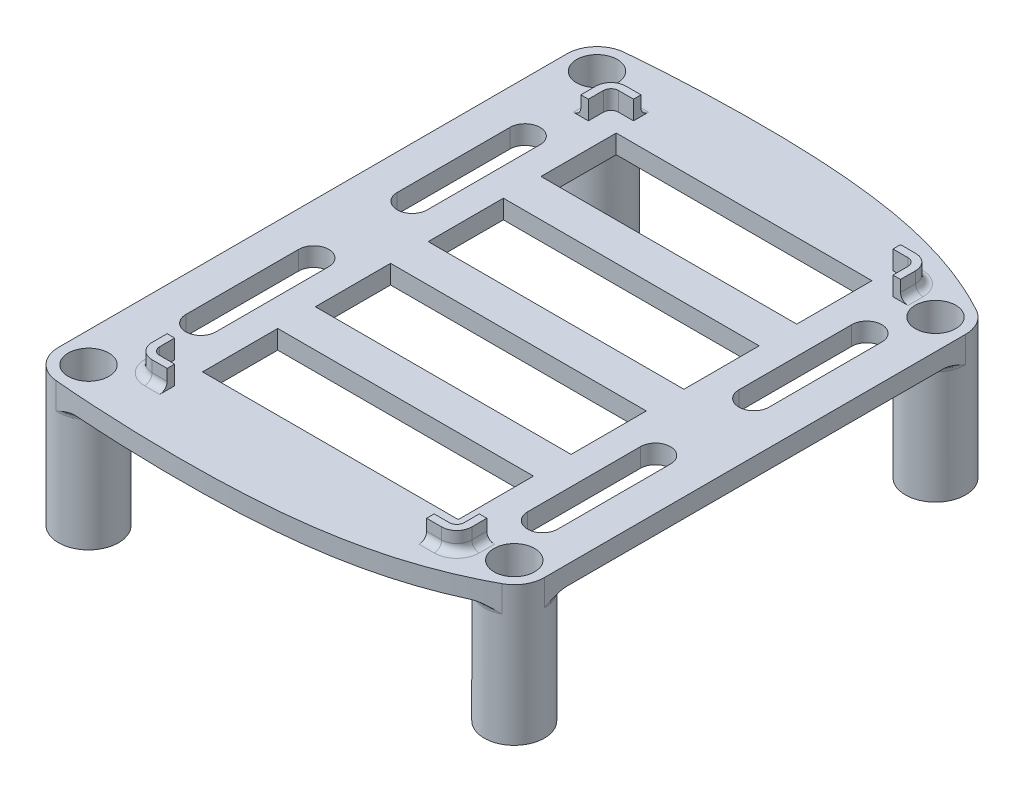
SolidWorks part; units mm, degrees
ref_plane "前视基准面" through (0, 0, 0) normal (0, 0, 1) x (1, 0, 0)
ref_plane "上视基准面" through (0, 0, 0) normal (0, 1, 0) x (1, 0, 0)
ref_plane "右视基准面" through (0, 0, 0) normal (1, 0, 0) x (0, 0, -1)
other "Configuration Table"
sketch "草图1" plane through (0, 0, 0) normal (0, 1, 0) x (1, 0, 0)
  line L0 (0, 35.4779) -> (0, -35.3561) construction
  line L1 (-47.5, 31) -> (-41.5, 31)
  line L2 (-47.5, 25) -> (-47.5, -25)
  line L3 (-47.5, -31) -> (-41.5, -31)
  line L4 (47.5, 25) -> (47.5, -25)
  line L5 (-47.5, 31) -> (47.5, -31) construction
  line L6 (-47.5, -31) -> (47.5, 31) construction
  line L9 (-41.5, 31) -> (-41.5, 41)
  line L11 (-29.5, 31) -> (-29.5, 41)
  line L12 (29.5, 31) -> (29.5, 41)
  line L14 (41.5, 31) -> (41.5, 41)
  line L15 (-78.7463, 0) -> (58.6748, 0) construction
  line L16 (41.5, -31) -> (41.5, -41)
  line L18 (29.5, -31) -> (29.5, -41)
  line L21 (-29.5, -31) -> (-29.5, -41)
  line L23 (-41.5, -31) -> (-41.5, -41)
  line L24 (-29.5, 31) -> (-3, 31)
  line L25 (41.5, 31) -> (47.5, 31)
  line L26 (41.5, -31) -> (47.5, -31)
  line L27 (-29.5, -31) -> (-3, -31)
  line L28 (47.5, 31) -> (50.8, 31)
  line L29 (-47.5, 31) -> (-50.8, 31)
  line L31 (-47.5, 25) -> (-50.8, 25)
  line L33 (47.5, 25) -> (50.8, 25)
  line L36 (47.5, -25) -> (50.8, -25)
  line L37 (47.5, -31) -> (50.8, -31)
  line L38 (-47.5, -31) -> (-50.8, -31)
  line L39 (-47.5, -25) -> (-50.8, -25)
  line L41 (-3, -33.8) -> (-3, -31)
  line L43 (-3, 33.8) -> (-3, 31)
  line L45 (3, 33.8) -> (3, 31)
  line L47 (3, -33.8) -> (3, -31)
  line L48 (3, 31) -> (29.5, 31)
  line L49 (3, -31) -> (29.5, -31)
  arc A0 (-41.5, 41) -> (-29.5, 41) centre (-35.5, 41) cw
  arc A1 (-41.5, -41) -> (-29.5, -41) centre (-35.5, -41) ccw
  arc A2 (41.5, -41) -> (29.5, -41) centre (35.5, -41) cw
  arc A3 (41.5, 41) -> (29.5, 41) centre (35.5, 41) ccw
  arc A4 (-50.8, 31) -> (-50.8, 25) centre (-50.8, 28) ccw
  circle A5 centre (-50.8, 28) radius 1.5
  circle A6 centre (50.8, 28) radius 1.5
  arc A7 (50.8, 31) -> (50.8, 25) centre (50.8, 28) cw
  circle A8 centre (50.8, -28) radius 1.5
  arc A9 (50.8, -31) -> (50.8, -25) centre (50.8, -28) ccw
  circle A10 centre (-50.8, -28) radius 1.5
  arc A11 (-50.8, -31) -> (-50.8, -25) centre (-50.8, -28) cw
  arc A12 (-3, 33.8) -> (3, 33.8) centre (0, 33.8) cw
  circle A13 centre (0, 33.8) radius 1.5
  circle A14 centre (0, -33.8) radius 1.5
  arc A15 (-3, -33.8) -> (3, -33.8) centre (0, -33.8) ccw
  point P0 (0, 0)
  dimension "D8" = 2.8
  dimension "D1" = 95
  dimension "D2" = 62
  dimension "D3" = 83
  dimension "D4" = 12
  dimension "D5" = 10
  dimension "D6" = 3.3
  dimension "D7" = 6
  dimension "D9" = 6
extrude "凸台-拉伸1" add sketch "草图1" against normal blind 15
sketch "草图2" plane through (0, -15, 0) normal (0, -1, 0) x (1, 0, 0)
  line L0 (-63.1336, 0) -> (63.5579, 0) construction
  line L1 (-57.0239, 31) -> (-3, 31)
  line L2 (-57.0239, 31) -> (-57.0239, 48.5806)
  line L3 (-57.0239, 48.5806) -> (57.0239, 48.5806)
  line L4 (57.0239, 31) -> (57.0239, 48.5806)
  line L5 (0, 56.9992) -> (0, -44.1169) construction
  line L6 (3, 33.8) -> (3, 31) construction
  line L7 (-3, 31) -> (-3, 33.8) construction
  line L8 (3, 33.8) -> (3, 31)
  line L9 (-3, 31) -> (-3, 33.8)
  line L10 (3, 31) -> (57.0239, 31)
  line L11 (3, -33.8) -> (3, -31)
  line L12 (-3, -31) -> (-3, -33.8)
  line L13 (-57.0239, -31) -> (-3, -31)
  line L14 (-57.0239, -31) -> (-57.0239, -48.5806)
  line L15 (-57.0239, -48.5806) -> (57.0239, -48.5806)
  line L16 (57.0239, -31) -> (57.0239, -48.5806)
  line L17 (3, -31) -> (57.0239, -31)
  arc A0 (3, 33.8) -> (-3, 33.8) centre (0, 33.8) ccw construction
  arc A1 (3, 33.8) -> (-3, 33.8) centre (0, 33.8) ccw
  arc A2 (3, -33.8) -> (-3, -33.8) centre (0, -33.8) cw
extrude "切除-拉伸1" cut sketch "草图2" against normal blind 11
sketch "草图3" plane through (0, -15, 0) normal (0, -1, 0) x (1, 0, 0)
  line L0 (47.5, 25) -> (47.5, -25) construction
  line L1 (-45, -28.5) -> (45, -28.5)
  line L2 (-45, -28.5) -> (-45, 28.5)
  line L3 (-45, 28.5) -> (45, 28.5)
  line L4 (45, -28.5) -> (45, 28.5)
  line L5 (-45, -28.5) -> (45, 28.5) construction
  line L6 (-45, 28.5) -> (45, -28.5) construction
  line L7 (-50.8, 31) -> (-3, 31) construction
  point P0 (0, 0)
  dimension "D1" = 2.5
  dimension "D2" = 2.5
extrude "切除-拉伸2" cut sketch "草图3" against normal blind 12
sketch "草图4" plane through (0, -4, 0) normal (0, -1, 0) x (1, 0, 0)
  line L0 (-29.5, 41) -> (-41.5, 41) construction
  line L1 (-71.7869, 0) -> (71.1524, 0) construction
  line L2 (0, 61.1393) -> (0, -47.8922) construction
  circle A0 centre (-35.5, 41) radius 2.8
  circle A1 centre (35.5, 41) radius 2.8
  circle A2 centre (35.5, -41) radius 2.8
  circle A3 centre (-35.5, -41) radius 2.8
extrude "凸台-拉伸2" add sketch "草图4" along normal blind 3.3 separate body
sketch "草图5" plane through (0, -7.3, 0) normal (0, -1, 0) x (1, 0, 0)
  line L0 (-58.868, 0) -> (56.1189, 0) construction
  line L1 (0, 46.5823) -> (0, -51.4835) construction
  circle A0 centre (-35.5, 41) radius 1.5
  circle A1 centre (35.5, 41) radius 1.5
  circle A2 centre (35.5, -41) radius 1.5
  circle A3 centre (-35.5, -41) radius 1.5
extrude "凸台-拉伸3" add sketch "草图5" along normal blind 1.3 separate body
sketch "草图6" plane through (0, -15, 0) normal (0, -1, 0) x (1, 0, 0)
  line L0 (-50.8, 31) -> (-3, 31) construction
  line L1 (-47.5, 31) -> (47.5, 31)
  line L2 (-47.5, 31) -> (-47.5, -31)
  line L3 (-47.5, -31) -> (47.5, -31)
  line L4 (47.5, 31) -> (47.5, -31)
  line L5 (50.8, -31) -> (3, -31) construction
extrude "切除-拉伸3" cut sketch "草图6" against normal blind 5
sketch "草图7" plane through (0, -3, 0) normal (0, -1, 0) x (1, 0, 0)
  line L0 (-60.2485, 0) -> (64.067, 0) construction
  line L1 (0, 41.3678) -> (0, -47.8169) construction
  line L2 (-30, -19) -> (30, -19)
  line L3 (-30, 21) -> (-2, 21)
  line L4 (-30, 21) -> (-30, 19)
  line L5 (-30, 19) -> (30, 19)
  line L6 (30, 21) -> (30, 19)
  line L7 (-30, 21) -> (30, 19) construction
  line L8 (-30, 19) -> (30, 21) construction
  line L9 (30, -21) -> (30, -19)
  line L10 (-30, -21) -> (-2, -21)
  line L11 (-30, -21) -> (-30, -19)
  line L12 (45, 28.5) -> (-45, 28.5) construction
  line L13 (-2, 28.5) -> (2, 28.5)
  line L14 (-2, 28.5) -> (-2, 21)
  line L16 (2, 28.5) -> (2, 21)
  line L18 (2, -28.5) -> (2, -21)
  line L19 (-2, -28.5) -> (2, -28.5)
  line L20 (-2, -28.5) -> (-2, -21)
  line L21 (2, 21) -> (30, 21)
  line L22 (2, -21) -> (30, -21)
  point P5 (0, 20)
  dimension "D1" = 19
  dimension "D2" = 2
  dimension "D3" = 60
  dimension "D4" = 4
extrude "凸台-拉伸4" add sketch "草图7" along normal blind 2.5 separate body
sketch "草图9" plane through (0, -10, 0) normal (0, -1, 0) x (1, 0, 0)
  line L0 (-45, 28.5) -> (45, 28.5) construction
  line L1 (41.5, 31) -> (32, 31)
  line L2 (41.5, 31) -> (41.5, 28.5)
  line L3 (41.5, 28.5) -> (32, 28.5)
  line L4 (32, 31) -> (32, 28.5)
  dimension "D1" = 9.5
extrude "切除-拉伸4" cut sketch "草图9" against normal blind 5
sketch "草图10" plane through (0, 0, 0) normal (0, 1, 0) x (1, 0, 0)
  line L1 (-34.25, -14) -> (34.25, -14)
  line L2 (-36.25, -12) -> (-36.25, 12)
  line L3 (-34.25, 14) -> (34.25, 14)
  line L4 (36.25, -12) -> (36.25, 12)
  line L5 (-36.25, -14) -> (36.25, 14) construction
  line L6 (-36.25, 14) -> (36.25, -14) construction
  arc A0 (-34.25, -14) -> (-36.25, -12) centre (-34.25, -12) cw
  arc A1 (34.25, -14) -> (36.25, -12) centre (34.25, -12) ccw
  arc A2 (34.25, 14) -> (36.25, 12) centre (34.25, 12) cw
  arc A3 (-36.25, 12) -> (-34.25, 14) centre (-34.25, 12) cw
  point P0 (0, 0)
  dimension "D3" = 2
  dimension "D1" = 72.5
  dimension "D2" = 28
extrude "切除-拉伸5" cut sketch "草图10" against normal through all
fillet "圆角1" radius 3 8 edges at (41.5, -2, 31) (29.5, -2, 31) (-29.5, -2, 31) (-41.5, -2, 31) (-41.5, -2, -31) (-29.5, -2, -31) (29.5, -2, -31) (41.5, -2, -31)
fillet "圆角3" radius 1 12 edges at (0, -3, -28.5) (-45, -3, 0) (0, -3, 28.5) (45, -3, 0) (-35.6642, -3, -13.4142) (0, -3, -14) (35.6642, -3, -13.4142) (36.25, -3, 0) (35.6642, -3, 13.4142) (0, -3, 14) (-35.6642, -3, 13.4142) (-36.25, -3, 0)
combine bodies "组合1" operation type add bodies to combine 111 121 115 109 112 113 116 110 118 119 114
fillet "圆角4" radius 1 40 edges at (-2, -3, 24.25) (-2, -3, -24.25) (-2, -3.2929, 28.2071) (-2, -3.2929, -28.2071) (-2, -4.75, 28.5) (-2, -4.75, -28.5) (-2, -5.5, 24.75) (-30, -3, 20) (16, -5.5, 21) (0, -5.5, 28.5) (-30, -3, -20) (-2, -5.5, -24.75) (0, -5.5, -28.5) (16, -5.5, -21) (-2, -4.25, 21) (-16, -5.5, 21) (-30, -4.25, 21) (-16, -3, 21) (2, -4.25, 21) (2, -5.5, 24.75) (2, -4.75, 28.5) (2, -3.2929, 28.2071) (2, -3, 24.25) (-30, -4.25, -21) (-16, -5.5, -21) (-2, -4.25, -21) (-16, -3, -21) (2, -5.5, -24.75) (2, -4.25, -21) (2, -3, -24.25) (2, -3.2929, -28.2071) (2, -4.75, -28.5) (-47.5, -5, 25) (-47.5, -5, -25) (-3, -5, -31) (3, -5, -31) (47.5, -5, -25) (47.5, -5, 25) (-3, -5, 31) (3, -5, 31)
sketch "草图11" plane through (0, 0, 0) normal (0, 1, 0) x (1, 0, 0)
  line L0 (-69.2433, 0) -> (76.7956, 0) construction
  circle A0 centre (0, 33.8) radius 4
  circle A1 centre (50.8, 28) radius 4
  circle A2 centre (0, -33.8) radius 4
  circle A3 centre (50.8, -28) radius 4
extrude "凸台-拉伸5" add sketch "草图11" along normal blind 16
sketch "草图12" plane through (0, 16, 0) normal (0, 1, 0) x (1, 0, 0)
  line L0 (-65.6793, 0) -> (77.8139, 0) construction
  circle A0 centre (0, 33.8) radius 1.5
  circle A1 centre (50.8, 28) radius 1.5
  circle A2 centre (0, -33.8) radius 1.5
  circle A3 centre (50.8, -28) radius 1.5
extrude "切除-拉伸6" cut sketch "草图12" against normal up to next
sketch "草图13" plane through (0, 16, 0) normal (0, 1, 0) x (1, 0, 0)
  line L0 (-55.9061, 0) -> (58.1408, 0) construction
  circle A0 centre (0, 33.8) radius 2.7
  circle A1 centre (50.8, 28) radius 2.7
  circle A2 centre (0, -33.8) radius 2.7
  circle A3 centre (50.8, -28) radius 2.7
extrude "切除-拉伸7" cut sketch "草图13" against normal blind 12.5
sketch "草图14" plane through (0, 16, 0) normal (0, 1, 0) x (1, 0, 0)
  line L0 (0, 33.8) -> (0, -33.8) construction
  line L1 (50.8, 28) -> (50.8, -28) construction
  line L2 (-60.003, 0) -> (68.6402, 0) construction
  line L3 (0, 33.8) -> (0, -33.8)
  line L4 (0, 33.8) -> (12.6031, 34.95) construction
  line L5 (12.6031, 34.95) -> (27.419, 34.7819) construction
  line L6 (27.419, 34.7819) -> (38.9454, 34.4297) construction
  line L7 (38.9454, 34.4297) -> (50.8, 28) construction
  line L8 (50.8, 28) -> (50.8, -28)
  line L9 (0, -33.8) -> (12.6031, -34.95) construction
  line L10 (12.6031, -34.95) -> (27.419, -34.7819) construction
  line L11 (27.419, -34.7819) -> (38.9454, -34.4297) construction
  line L12 (38.9454, -34.4297) -> (50.8, -28) construction
  line L13 (54.8, 28) -> (54.8, -28)
  line L14 (-4, 33.8) -> (-4, -33.8)
  line L15 (-4, 37.4516) -> (-4, -37.4516) construction
  line L16 (54.8, 30.381) -> (54.8, -30.381) construction
  arc A0 (3.9878, 34.1116) -> (3.9835, 34.1635) centre (0, 33.8) ccw
  arc A1 (52.7071, -31.5161) -> (54.8, -28) centre (50.8, -28) ccw
  arc A2 (3.9835, -34.1635) -> (3.9878, -34.1116) centre (0, -33.8) ccw
  circle A8 centre (50.8, 28) radius 1.5 construction
  circle A9 centre (0, -33.8) radius 4 construction
  circle A11 centre (50.8, 28) radius 4 construction
  circle A12 centre (0, 33.8) radius 4 construction
  arc A13 (-4, -33.8) -> (0, -37.8) centre (0, -33.8) ccw
  arc A15 (54.8, 28) -> (52.7071, 31.5161) centre (50.8, 28) ccw
  arc A16 (-0.3635, 37.7835) -> (-4, 33.8) centre (0, 33.8) ccw
  spline S0 degree 4 poles (0, 33.8) (12.6031, 34.95) (27.419, 34.7819) (38.9454, 34.4297) (50.8, 28) knots 0 0 0 0 0 1 1 1 1 1
  spline S1 degree 4 poles (0, -33.8) (12.6031, -34.95) (27.419, -34.7819) (38.9454, -34.4297) (50.8, -28) knots 0 0 0 0 0 1 1 1 1 1
  spline S2 degree 1 poles (-4, -37.4516) (54.8, -30.381) knots 0 0 1 1 construction
  spline S3 degree 1 poles (-4, 37.4516) (54.8, 30.381) knots 0 0 1 1 construction
  spline S4 degree 3 poles (54.8, -30.381) (54.2486, -30.68) (53.6303, -31.0154) (52.9472, -31.3859) (52.7924, -31.4698) (52.565, -31.5933) (52.1027, -31.841) (51.093, -32.3627) (49.5916, -33.0832) (47.1986, -34.1154) (44.1982, -35.2065) (39.3793, -36.5763) (33.3024, -37.691) (25.8804, -38.3646) (18.3191, -38.5854) (11.9591, -38.5008) (6.9036, -38.2973) (3.2926, -38.0869) (0.8055, -37.8906) (-0.7075, -37.7519) (-1.3947, -37.6892) (-2.5351, -37.5854) (-3.4138, -37.5051) (-4, -37.4516) knots -0.072135 -0.072135 -0.072135 -0.072135 -0.037252 -0.032891 -0.029088 -0.026907 -0.01981 -0.002368 0.032515 0.067399 0.137166 0.206933 0.346467 0.486001 0.625535 0.765069 0.834836 0.904603 0.967642 0.976363 0.991812 1.009254 1.044138 1.044138 1.044138 1.044138 only from (52.7071, -31.5161) to (-0.3635, -37.7835)
  spline S5 degree 3 poles (-4, 37.4516) (-3.4138, 37.5051) (-2.5351, 37.5854) (-1.3947, 37.6892) (-0.7075, 37.7519) (0.8055, 37.8906) (3.2926, 38.0869) (6.9036, 38.2973) (11.9591, 38.5008) (18.3191, 38.5854) (25.8804, 38.3646) (33.3024, 37.691) (39.3793, 36.5763) (44.1982, 35.2065) (47.1986, 34.1154) (49.5916, 33.0832) (51.093, 32.3627) (52.1027, 31.841) (52.565, 31.5933) (52.7924, 31.4698) (52.9472, 31.3859) (53.6303, 31.0154) (54.2486, 30.68) (54.8, 30.381) knots -0.072135 -0.072135 -0.072135 -0.072135 -0.037252 -0.01981 -0.00436 0.00436 0.067399 0.137166 0.206933 0.346467 0.486001 0.625535 0.765069 0.834836 0.904603 0.939487 0.974371 0.991812 0.99891 1.00109 1.004894 1.009254 1.044138 1.044138 1.044138 1.044138 only from (-0.3635, 37.7835) to (52.7071, 31.5161)
  point P11 (50.8, 0)
  point P17 (0, 0)
  dimension "D1" = 4
extrude "凸台-拉伸6" add sketch "草图14" along normal blind 2.5
sketch "草图15" plane through (0, 18.5, 0) normal (0, 1, 0) x (1, 0, 0)
  line L2 (-4, 33.8) -> (-4, -33.8)
  line L3 (54.8, -28) -> (54.8, 28)
  line L4 (-4, 33.8) -> (-4, -33.8)
  line L5 (54.8, -28) -> (54.8, 28)
  circle A0 centre (0, 33.8) radius 2.7
  circle A1 centre (50.8, 28) radius 2.7
  circle A2 centre (50.8, -28) radius 2.7
  circle A3 centre (0, -33.8) radius 2.7
  arc A4 (-0.3635, 37.7835) -> (-4, 33.8) centre (0, 33.8) ccw
  arc A5 (-4, -33.8) -> (-0.3635, -37.7835) centre (0, -33.8) ccw
  arc A6 (52.7071, -31.5161) -> (54.8, -28) centre (50.8, -28) ccw
  arc A7 (54.8, 28) -> (52.7071, 31.5161) centre (50.8, 28) ccw
  arc A8 (-0.3635, 37.7835) -> (-4, 33.8) centre (0, 33.8) ccw
  arc A9 (-4, -33.8) -> (-0.3635, -37.7835) centre (0, -33.8) ccw
  arc A10 (52.7071, -31.5161) -> (54.8, -28) centre (50.8, -28) ccw
  arc A11 (54.8, 28) -> (52.7071, 31.5161) centre (50.8, 28) ccw
  spline S2 degree 3 poles (-2546.4981, 1528.7201) (61.493, 26.0185) (56.6767, 29.3897) (52.1027, 31.841) (51.093, 32.3627) (49.5916, 33.0832) (47.1986, 34.1154) (44.1982, 35.2065) (39.3793, 36.5763) (33.3024, 37.691) (25.8804, 38.3646) (18.3191, 38.5854) (11.9591, 38.5008) (6.9036, 38.2973) (3.2926, 38.0869) (-15.5497, 36.6001) (-30.0191, 32.3563) (2942.6396, 619.4497) knots -0.238757 -0.238757 -0.238757 -0.238757 0.00109 0.008188 0.025629 0.060513 0.095397 0.165164 0.234931 0.374465 0.513999 0.653533 0.793067 0.862834 0.932601 0.99564 1.935016 1.935016 1.935016 1.935016 only from (52.7071, 31.5161) to (-0.3635, 37.7835)
  spline S3 degree 3 poles (2942.5968, -619.4413) (-30.0189, -32.3564) (-15.5496, -36.6001) (3.2926, -38.0869) (6.9036, -38.2973) (11.9591, -38.5008) (18.3191, -38.5854) (25.8804, -38.3646) (33.3024, -37.691) (39.3793, -36.5763) (44.1982, -35.2065) (47.1986, -34.1154) (49.5916, -33.0832) (51.093, -32.3627) (52.1027, -31.841) (56.6765, -29.3898) (61.4926, -26.0188) (-2546.1335, -1528.51) knots -0.963009 -0.963009 -0.963009 -0.963009 -0.023637 0.039401 0.109168 0.178935 0.318469 0.458004 0.597538 0.737072 0.806839 0.876606 0.911489 0.946373 0.963815 0.970912 1.210749 1.210749 1.210749 1.210749 only from (-0.3635, -37.7835) to (52.7071, -31.5161)
  spline S4 degree 3 poles (52.7071, 31.5161) (52.6884, 31.5263) (52.5461, 31.6034) (52.1027, 31.841) (51.093, 32.3627) (49.5916, 33.0832) (47.1986, 34.1154) (44.1982, 35.2065) (39.3793, 36.5763) (33.3024, 37.691) (25.8804, 38.3646) (18.3191, 38.5854) (11.9591, 38.5008) (6.9036, 38.2973) (3.2926, 38.0869) (0.8821, 37.8967) (-0.2881, 37.7903) (-0.3635, 37.7835) knots 0 0 0 0 0.00109 0.008188 0.025629 0.060513 0.095397 0.165164 0.234931 0.374465 0.513999 0.653533 0.793067 0.862834 0.932601 0.99564 1 1 1 1
  spline S5 degree 3 poles (-0.3635, -37.7835) (-0.2881, -37.7903) (0.8821, -37.8967) (3.2926, -38.0869) (6.9036, -38.2973) (11.9591, -38.5008) (18.3191, -38.5854) (25.8804, -38.3646) (33.3024, -37.691) (39.3793, -36.5763) (44.1982, -35.2065) (47.1986, -34.1154) (49.5916, -33.0832) (51.093, -32.3627) (52.1027, -31.841) (52.5461, -31.6034) (52.6884, -31.5263) (52.7071, -31.5161) knots -0.027998 -0.027998 -0.027998 -0.027998 -0.023637 0.039401 0.109168 0.178935 0.318469 0.458004 0.597538 0.737072 0.806839 0.876606 0.911489 0.946373 0.963815 0.970912 0.972002 0.972002 0.972002 0.972002
  dimension "D1" = 0
extrude "切除-拉伸9" cut sketch "草图15" against normal up to next contours A0 | A1 | A3 | A2
sketch "草图18" plane through (0, 18.5, 0) normal (0, 1, 0) x (1, 0, 0)
  line L0 (-4, 0) -> (54.8, 0) construction
  line L1 (-4, 33.8) -> (-4, -33.8) construction
  line L2 (54.8, 28) -> (54.8, -28) construction
  line L3 (4.15, 29.5) -> (4.15, -29.5)
  line L4 (6.15, 30.5) -> (44.65, 30.5)
  line L5 (5.15, 29.5) -> (5.15, -29.5)
  line L6 (6.15, -30.5) -> (44.65, -30.5)
  line L7 (45.65, 29.5) -> (45.65, -29.5)
  line L8 (5.15, 30.5) -> (45.65, -30.5) construction
  line L9 (5.15, -30.5) -> (45.65, 30.5) construction
  line L10 (6.15, -31.5) -> (44.65, -31.5)
  line L11 (46.65, 29.5) -> (46.65, -29.5)
  line L12 (6.15, 31.5) -> (44.65, 31.5)
  line L13 (8.15, 31.5) -> (8.15, 30.5)
  line L14 (4.15, 27.5) -> (5.15, 27.5)
  line L15 (8.15, -31.5) -> (8.15, -30.5)
  line L16 (4.15, -27.5) -> (5.15, -27.5)
  line L17 (25.4, 35.8449) -> (25.4, -33.7801) construction
  line L18 (46.65, -27.5) -> (45.65, -27.5)
  line L19 (42.65, -31.5) -> (42.65, -30.5)
  line L20 (46.65, 27.5) -> (45.65, 27.5)
  line L21 (42.65, 31.5) -> (42.65, 30.5)
  arc A0 (44.65, -30.5) -> (45.65, -29.5) centre (44.65, -29.5) ccw
  arc A1 (5.15, -29.5) -> (6.15, -30.5) centre (6.15, -29.5) ccw
  arc A2 (44.65, 30.5) -> (45.65, 29.5) centre (44.65, 29.5) cw
  arc A3 (6.15, 30.5) -> (5.15, 29.5) centre (6.15, 29.5) ccw
  arc A4 (4.15, -29.5) -> (6.15, -31.5) centre (6.15, -29.5) ccw
  arc A5 (44.65, -31.5) -> (46.65, -29.5) centre (44.65, -29.5) ccw
  arc A6 (44.65, 31.5) -> (46.65, 29.5) centre (44.65, 29.5) cw
  arc A7 (6.15, 31.5) -> (4.15, 29.5) centre (6.15, 29.5) ccw
  point P6 (25.4, 0)
  dimension "D3" = 1
  dimension "D1" = 61
  dimension "D2" = 40.5
  dimension "D5" = 2
  dimension "D6" = 2
  dimension "D4" = 1
extrude "凸台-拉伸8" add sketch "草图18" along normal blind 2.5 contours L3 A4 L10 L15 L6 A1 L5 L16 | L10 A5 L11 L18 L7 A0 L6 L19 | A6 L12 L21 L4 A2 L7 L20 L11 | L12 A7 L3 L14 L5 A3 L4 L13
fillet "圆角5" radius 1 12 edges at (43.65, 18.5, -31.5) (46.65, 18.5, -28.5) (43.65, 18.5, 31.5) (46.65, 18.5, 28.5) (7.15, 18.5, 31.5) (4.7358, 18.5, 30.9142) (7.15, 18.5, -31.5) (4.15, 18.5, -28.5) (46.0642, 18.5, -30.9142) (46.0642, 18.5, 30.9142) (4.15, 18.5, 28.5) (4.7358, 18.5, -30.9142)
sketch "草图19" plane through (47.5, 0, 0) normal (1, 0, 0) x (0, 0, -1)
  line L0 (0, 9.0073) -> (0, -13.2174) construction
  line L1 (0, 9.0073) -> (0, -13.2174) construction
  line L2 (0, 9.0073) -> (0, -13.2174) construction
  line L3 (-24, 0) -> (24, 0) construction
  line L4 (0, 3.85) -> (0, 0)
  line L5 (-1.5, 16) -> (-1.5, 3.9365)
  line L6 (28, 16) -> (-28, 16) construction
  line L7 (0, 3.85) -> (0, 16)
  line L8 (0, 16) -> (-1.5, 16)
  arc A0 (-1.75, 2.9682) -> (0, 0) centre (0, 2) ccw
  arc A1 (-1.5, 3.9365) -> (-1.75, 2.9682) centre (-3.5, 3.9365) cw
  dimension "D3" = 2
  dimension "D5" = 2
  dimension "D1" = 0
  dimension "D2" = 2
  dimension "D4" = 1.5
sketch "草图20" plane through (0, 0, 0) normal (0, 1, 0) x (1, 0, 0)
  line L1 (-62.2942, 50.7869) -> (60.6636, 50.7869)
  line L2 (-62.2942, 50.7869) -> (-62.2942, -49.2595)
  line L3 (-62.2942, -49.2595) -> (60.6636, -49.2595)
  line L4 (60.6636, 50.7869) -> (60.6636, -49.2595)
extrude "切除-拉伸11" cut sketch "草图20" against normal through all
fillet "圆角6" radius 1 4 edges at (47.3628, 16, -25.9541) (47.3628, 16, 25.9541) (2.9541, 16, 31.1031) (2.9541, 16, -31.1031)
sketch "草图23" plane through (0, 18.5, 0) normal (0, 1, 0) x (1, 0, 0)
  line L0 (-19.8345, 0) -> (61.1822, 0) construction
  line L1 (25.4, 5.0119) -> (25.4, 48.6626) construction
  line L2 (8.4, 12.9521) -> (8.4, 2.9521)
  line L3 (8.4, 12.9521) -> (42.4, 12.9521)
  line L4 (42.4, 12.9521) -> (42.4, 2.9521)
  line L5 (8.4, 27.9521) -> (42.4, 27.9521)
  line L6 (8.4, 27.9521) -> (8.4, 17.9521)
  line L7 (8.4, 17.9521) -> (42.4, 17.9521)
  line L8 (42.4, 27.9521) -> (42.4, 17.9521)
  line L9 (8.4, 27.9521) -> (42.4, 17.9521) construction
  line L10 (8.4, 17.9521) -> (42.4, 27.9521) construction
  line L11 (8.4, 2.9521) -> (42.4, 2.9521)
  line L12 (8.4, -2.0479) -> (8.4, -12.0479)
  line L13 (8.4, -2.0479) -> (42.4, -2.0479)
  line L14 (42.4, -2.0479) -> (42.4, -12.0479)
  line L15 (8.4, -12.0479) -> (42.4, -12.0479)
  line L16 (8.4, -17.0479) -> (8.4, -27.0479)
  line L17 (8.4, -17.0479) -> (42.4, -17.0479)
  line L18 (42.4, -17.0479) -> (42.4, -27.0479)
  line L19 (8.4, -27.0479) -> (42.4, -27.0479)
  line L20 (2.6827, 21.5481) -> (2.6827, 6.5481) construction
  line L21 (4.6827, 21.5481) -> (4.6827, 6.5481)
  line L22 (0.6827, 21.5481) -> (0.6827, 6.5481)
  line L23 (48.1173, 21.5481) -> (48.1173, 6.5481) construction
  line L24 (46.1173, 21.5481) -> (46.1173, 6.5481)
  line L25 (50.1173, 21.5481) -> (50.1173, 6.5481)
  line L26 (48.1173, -21.5481) -> (48.1173, -6.5481) construction
  line L27 (46.1173, -21.5481) -> (46.1173, -6.5481)
  line L28 (50.1173, -21.5481) -> (50.1173, -6.5481)
  line L29 (2.6827, -21.5481) -> (2.6827, -6.5481) construction
  line L30 (4.6827, -21.5481) -> (4.6827, -6.5481)
  line L31 (0.6827, -21.5481) -> (0.6827, -6.5481)
  arc A0 (4.6827, 21.5481) -> (0.6827, 21.5481) centre (2.6827, 21.5481) ccw
  arc A1 (0.6827, 6.5481) -> (4.6827, 6.5481) centre (2.6827, 6.5481) ccw
  arc A2 (46.1173, 21.5481) -> (50.1173, 21.5481) centre (48.1173, 21.5481) cw
  arc A3 (50.1173, 6.5481) -> (46.1173, 6.5481) centre (48.1173, 6.5481) cw
  arc A4 (46.1173, -21.5481) -> (50.1173, -21.5481) centre (48.1173, -21.5481) ccw
  arc A5 (50.1173, -6.5481) -> (46.1173, -6.5481) centre (48.1173, -6.5481) ccw
  arc A6 (4.6827, -21.5481) -> (0.6827, -21.5481) centre (2.6827, -21.5481) cw
  arc A7 (0.6827, -6.5481) -> (4.6827, -6.5481) centre (2.6827, -6.5481) cw
  point P5 (25.4, 22.9521)
  point P24 (2.6827, 14.0481)
  point P31 (48.1173, 14.0481)
  point P38 (48.1173, -14.0481)
  point P45 (2.6827, -14.0481)
  dimension "D5" = 2
  dimension "D1" = 34
  dimension "D2" = 10
  dimension "D4" = 15
  dimension "D3" = 4
extrude "切除-拉伸12" cut sketch "草图23" against normal through all
